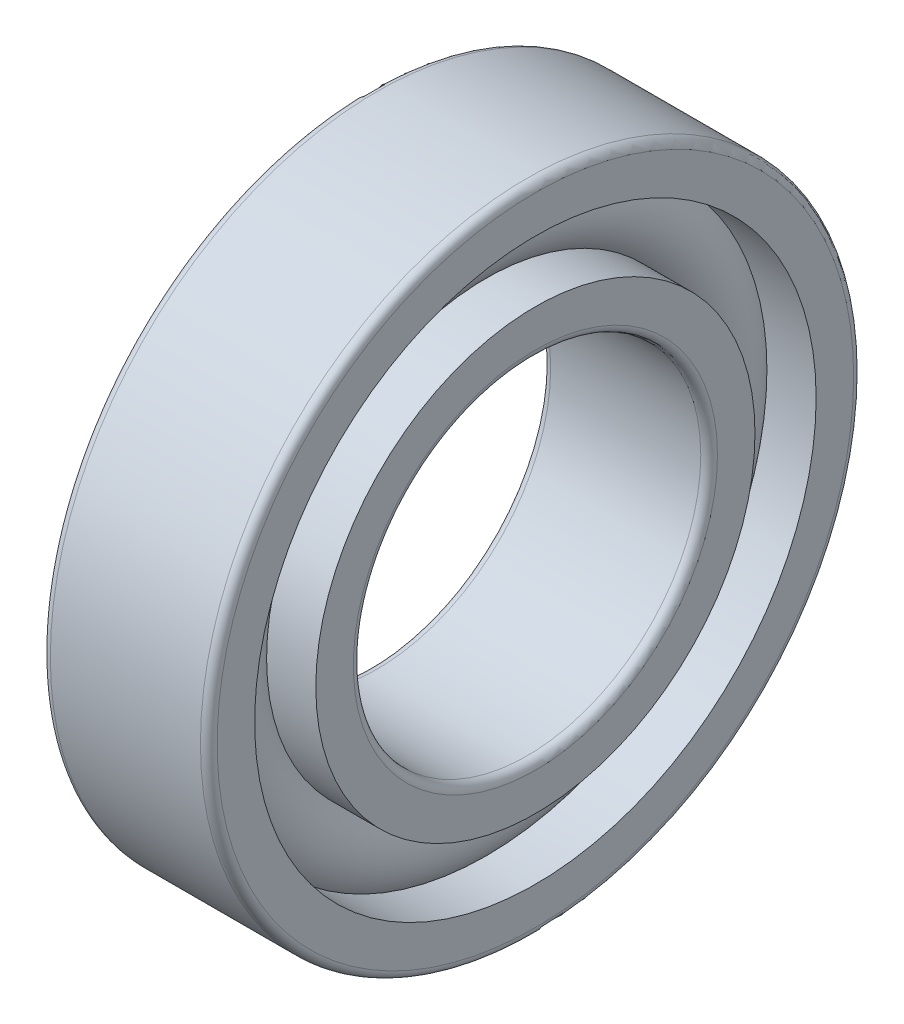
SolidWorks part; units mm, degrees
ref_plane "Plane1" through (0, 0, 0) normal (0, 0, 1) x (1, 0, 0)
ref_plane "Plane2" through (0, 0, 0) normal (0, 1, 0) x (1, 0, 0)
ref_plane "Plane3" through (0, 0, 0) normal (1, 0, 0) x (0, 0, -1)
sketch "Clipboard" plane through (0, 0, 0) normal (0, 0, 1) x (1, 0, 0)
  line L0 (-10, 0) -> (10, 0) construction
  line L1 (0, 0) -> (22.3471, -0.7804)
  line L2 (0, 0) -> (17.989, 0.6282)
  line L3 (0, 0) -> (22.3471, -0.7804)
  line L4 (0, 0) -> (-22.3573, -0.3902)
  dimension "BallCLRad" = 18
sketch "CagSpiSke" plane through (0, 0, 0) normal (0, 0, 1) x (1, 0, 0)
  line L0 (0.33, 17.45) -> (0.33, 18.55)
  line L1 (0.33, 18.55) -> (-0.33, 18.55)
  line L2 (-0.33, 18.55) -> (-0.33, 17.45)
  line L3 (-0.33, 17.45) -> (0.33, 17.45)
  line L4 (-20.6375, 0) -> (20.6375, 0) construction
  line L5 (0, 0) -> (0, 23.7692) construction
  dimension "OD" = 37.1
  dimension "ID" = 34.9
revolve "CageSpine" add sketch "CagSpiSke" angle 0.001 about L4 reverse direction yes
ref_axis "Axis1" through (-50, 0, 0) along (1, 0, 0)
sketch "CagBalSke" plane through (0, 0, 0) normal (0, 0, 1) x (1, 0, 0)
  line L0 (-3.63, 18) -> (3.63, 18)
  line L1 (-1.905, 18) -> (1.905, 18) construction
  line L2 (-10, 0) -> (10, 0) construction
  line L3 (0, 0) -> (0, 24) construction
  arc A0 (3.63, 18) -> (-3.63, 18) centre (0, 18) cw
  dimension "BallCLRad" = 18
revolve "CageBall" [suppressed] add sketch "CagBalSke" angle 360 about L1 reverse direction yes
pattern_circular "CageBalls" [suppressed] count 2 every 180 about axis through (-50, 0, 0) along (1, 0, 0)
sketch "CagTrmODSke" plane through (0, 0, 0) normal (0, 0, 1) x (1, 0, 0)
  line L0 (3.631, 18.55) -> (3.631, 21.631)
  line L1 (3.631, 21.631) -> (-3.631, 21.631)
  line L2 (-3.631, 21.631) -> (-3.631, 18.55)
  line L3 (-3.631, 18.55) -> (3.631, 18.55)
  line L4 (-20.6375, 0) -> (20.6375, 0) construction
  line L5 (0, 0) -> (0, 25) construction
  dimension "Width" = 7.262
  dimension "ID" = 37.1
  dimension "OD" = 43.262
revolve "CageTrimOD" [suppressed] cut sketch "CagTrmODSke" angle 360 about L4 reverse direction yes
sketch "CagTrmIDSke" plane through (0, 0, 0) normal (0, 0, 1) x (1, 0, 0)
  line L0 (3.631, 14.371) -> (3.631, 17.45)
  line L1 (3.631, 17.45) -> (-3.631, 17.45)
  line L2 (-3.631, 17.45) -> (-3.631, 14.371)
  line L3 (-3.631, 14.371) -> (3.631, 14.371)
  line L4 (-20.6375, 0) -> (20.6375, 0) construction
  line L5 (0, 0) -> (0, 25) construction
  dimension "Width" = 7.262
  dimension "ID" = 28.742
  dimension "OD" = 34.9
revolve "CageTrimID" [suppressed] cut sketch "CagTrmIDSke" angle 360 about L4 reverse direction yes
sketch "BalSimSke" plane through (0, 0, 0) normal (0, 0, 1) x (1, 0, 0)
  line L0 (-10, 0) -> (10, 0) construction
  line L1 (-10, 18) -> (10, 18) construction
  line L2 (0, 0) -> (0, 23) construction
  circle A0 centre (0, 18) radius 3.3
  dimension "BallCLRad" = 18
  dimension "Ball_diameter" = 6.6
revolve "BallsSimplified" add sketch "BalSimSke" angle 360 about L0
sketch "BalDetSke" plane through (0, 0, 0) normal (0, 0, 1) x (1, 0, 0)
  line L0 (-3.3, 18) -> (3.3, 18)
  line L1 (-1.905, 18) -> (1.905, 18) construction
  line L2 (0, 0) -> (0, 25) construction
  arc A0 (3.3, 18) -> (-3.3, 18) centre (0, 18) cw
  dimension "BallCLRad" = 18
  dimension "Ball_diameter" = 6.6
revolve "BallDetailed" [suppressed] add sketch "BalDetSke" angle 360 about L1 reverse direction yes
sketch "InnRacSke" plane through (0, 0, 0) normal (0, 0, 1) x (1, 0, 0)
  line L0 (-2.426, 15.8) -> (-6, 15.8)
  line L1 (-6, 15.8) -> (-6, 13.1)
  line L2 (-5.4, 12.5) -> (5.4, 12.5)
  line L3 (6, 13.1) -> (6, 15.8)
  line L4 (6, 15.8) -> (2.426, 15.8)
  line L5 (-20.6375, 0) -> (20.6375, 0) construction
  line L6 (0, 0) -> (0, 30) construction
  arc A0 (-6, 13.1) -> (-5.4, 12.5) centre (-5.4, 13.1) ccw
  arc A1 (5.4, 12.5) -> (6, 13.1) centre (5.4, 13.1) ccw
  arc A2 (2.426, 15.8) -> (-2.426, 15.8) centre (0, 18) cw
  dimension "BallCLRad" = 18
  dimension "Fillet_radius" = 0.6
  dimension "Ball_diameter" = 6.55
  dimension "ID" = 25
  dimension "OD" = 31.6
  dimension "Width" = 12
revolve "InnerRace" add sketch "InnRacSke" angle 360 about L5 reverse direction yes
sketch "OutRacSke" plane through (0, 0, 0) normal (0, 0, 1) x (1, 0, 0)
  line L0 (-2.426, 20.2) -> (-6, 20.2)
  line L1 (-6, 20.2) -> (-6, 22.9)
  line L2 (-5.4, 23.5) -> (5.4, 23.5)
  line L3 (6, 22.9) -> (6, 20.2)
  line L4 (6, 20.2) -> (2.426, 20.2)
  line L5 (-20.6375, 0) -> (20.6375, 0) construction
  line L6 (0, 0) -> (0, 30) construction
  arc A0 (-6, 22.9) -> (-5.4, 23.5) centre (-5.4, 22.9) cw
  arc A1 (5.4, 23.5) -> (6, 22.9) centre (5.4, 22.9) cw
  arc A2 (2.426, 20.2) -> (-2.426, 20.2) centre (0, 18) ccw
  dimension "BallCLRad" = 18
  dimension "Fillet_radius" = 0.6
  dimension "Ball_diameter" = 6.55
  dimension "Width" = 12
revolve "OuterRace" add sketch "OutRacSke" angle 360 about L5 reverse direction yes
pattern_circular "BallsDetailed" [suppressed] count 2 every 180 about axis through (-50, 0, 0) along (1, 0, 0)
equation "\"BallCLRad@Clipboard\" = ( \"OD@OutRacSke\" + \"ID@InnRacSke\" ) / 4"
equation "\"BallCLRad@BalSimSke\" = \"BallCLRad@Clipboard\""
equation "\"BallCLRad@BalDetSke\" = \"BallCLRad@Clipboard\""
equation "\"BallCLRad@InnRacSke\" = \"BallCLRad@Clipboard\""
equation "\"BallCLRad@OutRacSke\" = \"BallCLRad@Clipboard\""
equation "\"Ball_diameter@InnRacSke\" = \"Ball_diameter@BalDetSke\" - 0.05"
equation "\"Ball_diameter@OutRacSke\" = \"Ball_diameter@BalDetSke\" - 0.05"
equation "\"Ball_diameter@BalSimSke\" = \"Ball_diameter@BalDetSke\""
equation "\"Width@OutRacSke\" = \"Width@InnRacSke\""
equation "\"Fillet_radius@OutRacSke\" = \"Fillet_radius@InnRacSke\""
equation "\"Max_count@Clipboard\" = int( 3.14159265 / atn(( \"Ball_diameter@BalDetSke\" / 2) / sqr( \"BallCLRad@Clipboard\"  *  \"BallCLRad@Clipboard\" - ( \"Ball_diameter@BalDetSke\" / 2) *  ( \"Ball_diameter@BalDetSke\" / 2))))"
equation "\"Max_count@Clipboard\" = ((sgn( \"Max_count@Clipboard\" - \"Count@Clipboard\" )-1)*( \"Max_count@Clipboard\" - \"Count@Clipboard\" ))/-2+ \"Count@Clipboard\""
equation "\"Count@BallsDetailed\" = int( \"Show_count@Clipboard\" ) "
equation "\"Count@BallsDetailed\" = ((sgn( \"Count@BallsDetailed\" - \"Max_count@Clipboard\" )-1)*( \"Count@BallsDetailed\" - \"Max_count@Clipboard\" ))/-2+ \"Max_count@Clipboard\""
equation "\"Count@BallsDetailed\" = ((sgn( \"Count@BallsDetailed\" - \"Min_count@Clipboard\" )+1)*( \"Count@BallsDetailed\" - \"Min_count@Clipboard\"))/2 +\"Min_count@Clipboard\""
equation "\"Angle@BallsDetailed\" = 360.0 / \"Max_count@Clipboard\""
equation "\"BallCLRad@CagBalSke\" = \"BallCLRad@Clipboard\""
equation "\"Count@CageBalls\" = \"Count@BallsDetailed\""
equation "\"Angle@CageBalls\" = \"Angle@BallsDetailed\""
equation "\"Angle@CageSpine\" =  \"Angle@CageBalls\" * ( \"Count@CageBalls\" -1 + int( \"Count@CageBalls\" / \"Max_count@Clipboard\" ) )  + 0.001 -  int( \"Count@CageBalls\" / \"Max_count@Clipboard\" ) * 0.001"
equation "\"Angle@CageSpine\" =  \"Angle@CageSpine\" * int( \"Min_count@Clipboard\" / 2) + int(1 / \"Min_count@Clipboard\")  * 0.001"
equation "\"CageWallOD@CagBalSke\" =  \"Ball_diameter@BalDetSke\" * 1.1"
equation "\"Thickness@CagSpiSke\" =  \"Ball_diameter@BalDetSke\" * 0.1"
equation "\"OD@CagTrmODSke\" = \"BallCLRad@Clipboard\" * 2 + \"CageWallOD@CagBalSke\" + 0.002"
equation "\"ID@CagTrmODSke\" = \"BallCLRad@Clipboard\" * 2 + \"Ball_diameter@BalDetSke\" / 6"
equation "\"OD@CagTrmIDSke\" = \"BallCLRad@Clipboard\" * 2 - \"Ball_diameter@BalDetSke\" / 6"
equation "\"ID@CagTrmIDSke\" = \"BallCLRad@Clipboard\" * 2 - \"CageWallOD@CagBalSke\" + 0.002"
equation "\"OD@CagSpiSke\" = \"ID@CagTrmODSke\""
equation "\"ID@CagSpiSke\" = \"OD@CagTrmIDSke\""
equation "\"Width@CagTrmODSke\" = \"CageWallOD@CagBalSke\" + 0.002"
equation "\"Width@CagTrmIDSke\" = \"CageWallOD@CagBalSke\" + 0.002"
